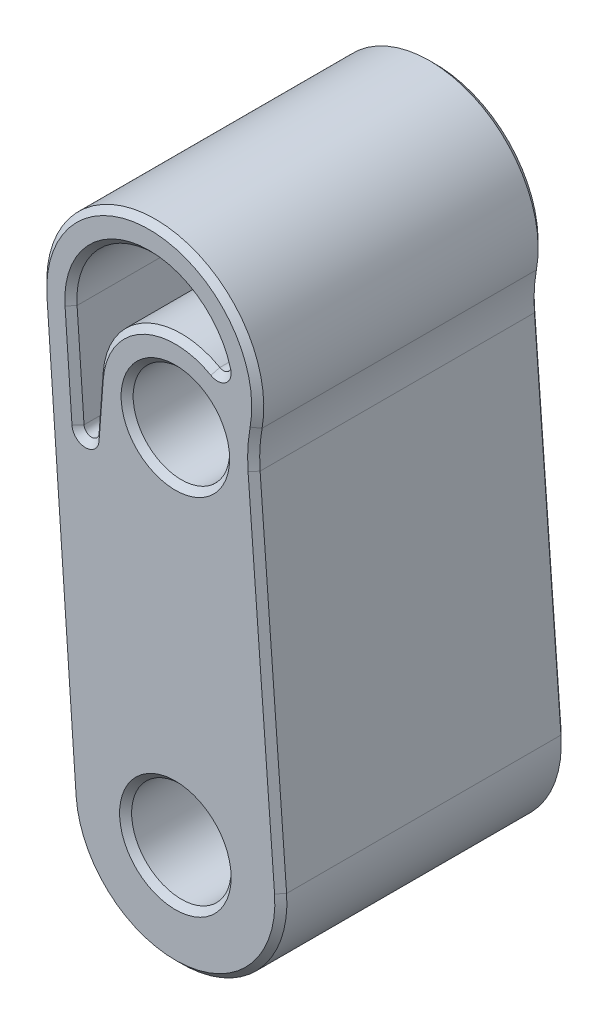
SolidWorks part; units mm, degrees
ref_plane "Front" through (0, 0, 0) normal (0, 0, 1) x (1, 0, 0)
ref_plane "Top" through (0, 0, 0) normal (0, 1, 0) x (1, 0, 0)
ref_plane "Right" through (0, 0, 0) normal (1, 0, 0) x (0, 0, -1)
sketch "Sketch1" plane through (0, 0, 0) normal (0, 0, 1) x (1, 0, 0)
  line L3 (-2.6, 0) -> (-1.6, 0) construction
  line L23 (1.65, -12) -> (2.65, -12) construction
  line L33 (-2.5927, 0.195) -> (-3.4901, -11.7375)
  line L34 (3.4901, -11.7375) -> (2.5927, 0.195)
  circle A0 centre (0, 0) radius 2.6 construction
  circle A3 centre (0, 0) radius 1.6
  circle A12 centre (0, -12) radius 1.65
  circle A13 centre (0, -12) radius 4.25 construction
  arc A22 (-2.5927, 0.195) -> (2.5927, 0.195) centre (0, 0) cw
  arc A28 (-3.4901, -11.7375) -> (3.4901, -11.7375) centre (0, -12) ccw
  dimension "D1" = 3.2
  dimension "D3" = 8.5
  dimension "D6" = 3.3
  dimension "D7" = 3.5
  dimension "D2" = 1
  dimension "D5" = 12
extrude "Boss-Extrude1" add sketch "Sketch1" along normal mid plane 9.5 contours A3 region at (0, -7.006, 0)
sketch "Sketch2" plane through (0, 0, 0) normal (0, 0, 1) x (1, 0, 0)
  line L0 (-3.4915, -12.2435) -> (-4.4576, 1.6074)
  line L1 (0, 0) -> (0, 8.0844) construction
  line L2 (0, 0) -> (-0.8664, 1.8579) construction
  line L3 (-0.8664, 1.8579) -> (-2.2187, 4.7581) construction
  line L4 (-2.2187, 4.7581) -> (-2.3878, 5.1206) construction
  arc A0 (-4.4576, 1.6074) -> (2.5206, 0.6378) centre (-0.8664, 1.8579) cw
  circle A1 centre (0, 0) radius 5.25 construction
  arc A2 (-3.4901, -11.7375) -> (3.4901, -11.7375) centre (0, -12) ccw construction
  arc A4 (2.5927, 0.195) -> (-2.5927, 0.195) centre (0, 0) ccw construction
  dimension "D2" = 10.5
  dimension "D4" = 3.6
  dimension "D1" = 0.4
  dimension "D3" = 25
extrude "Spring" add sketch "Sketch2" along normal through all and the other way through all thin thin type one direction wall 1
fillet "Spring Inside Fillets" radius 0.25 2 edges at (-2.9891, -5.0754, 0) (1.7324, 1.9388, 0)
fillet "Spring Outside Fillets" radius 5 1 edges at (2.5206, 0.6378, 0)
chamfer "Deburs" distance 0.2 angle 45 26 edges at (1.6, 0, -4.75) (1.65, -12, -4.75) (-1.3048, 4.4207, -4.75) (1.5529, 2.2861, -4.75) (-2.9804, -1.8672, -4.75) (-3.3446, 0.0212, -4.75) (0.253, -15.4908, -4.75) (3.0505, -5.8916, -4.75) (-1.2267, 2.2924, -4.75) (2.6034, 0.5883, -4.75) (-0.6702, 5.4526, -4.75) (-3.9746, -5.3181, -4.75) (1.65, -12, 4.75) (1.6, 0, 4.75) (1.5529, 2.2861, 4.75) (-1.3048, 4.4207, 4.75) (-3.3446, 0.0212, 4.75) (-2.9804, -1.8672, 4.75) (-0.6702, 5.4526, 4.75) (2.6034, 0.5883, 4.75) (-1.2267, 2.2924, 4.75) (3.0505, -5.8916, 4.75) (0.253, -15.4908, 4.75) (-3.9746, -5.3181, 4.75) (-2.6615, -0.7205, -4.75) (-2.6615, -0.7205, 4.75)
sketch "Sketch3" plane through (-4.3245, -0.3016, 0) normal (-0.9976, -0.0696, 0) x (0, 0, 1)
  line L1 (0, -0.5863) -> (0, -9.4709) construction
  line L6 (4.55, 1.9137) -> (-4.55, 1.9137) construction
  line L8 (4.55, -11.9709) -> (-4.55, -11.9709) construction
  point P0 (0, -9.4153)
  dimension "D1" = 2.5
  dimension "D2" = 2.5
sketch "Sketch4" plane through (-4.3245, -0.3016, 0) normal (-0.9976, -0.0696, 0) x (0, 0, 1)
  line L0 (0, -0.5863) -> (0, -9.4709)
  line L1 (-2, -2.5863) -> (0, -0.5863)
  line L2 (0, -0.5863) -> (2, -2.5863)
  line L3 (0, -0.5863) -> (0, -9.4709) construction
  line L6 (0, -11.9519) -> (0, 0.0141) construction
  point P5 (0, -10.1947)
  point P8 (0, -11.0942)
  point P9 (0, -1.4252)
  point P10 (0, -1.0863)
  dimension "D1" = 45
  dimension "D2" = 2
extrude "Arrow Point" add sketch "Sketch4" along normal blind 0.2 draft 55 thin contours L1 | L2 thin type one direction wall 0.8
sketch "Sketch5" plane through (-4.3245, -0.3016, 0) normal (-0.9976, -0.0696, 0) x (0, 0, 1)
  line L0 (0, -0.9902) -> (0, -9.4709)
  line L1 (0, -0.5863) -> (0, -9.4709) construction
  point P2 (0, -11.0942)
extrude "Arrow Shaft" add sketch "Sketch5" along normal blind 0.2 draft 55 thin thin type mid plane wall 0.8
equation "\"D1@Sketch1\"=\"Hardware Clearance Hole Diameter@Box Assy.Assembly\"+.05mm"
equation "\"D6@Sketch1\"=\"Hardware Clearance Hole Diameter@Box Assy.Assembly\"+.15mm"
